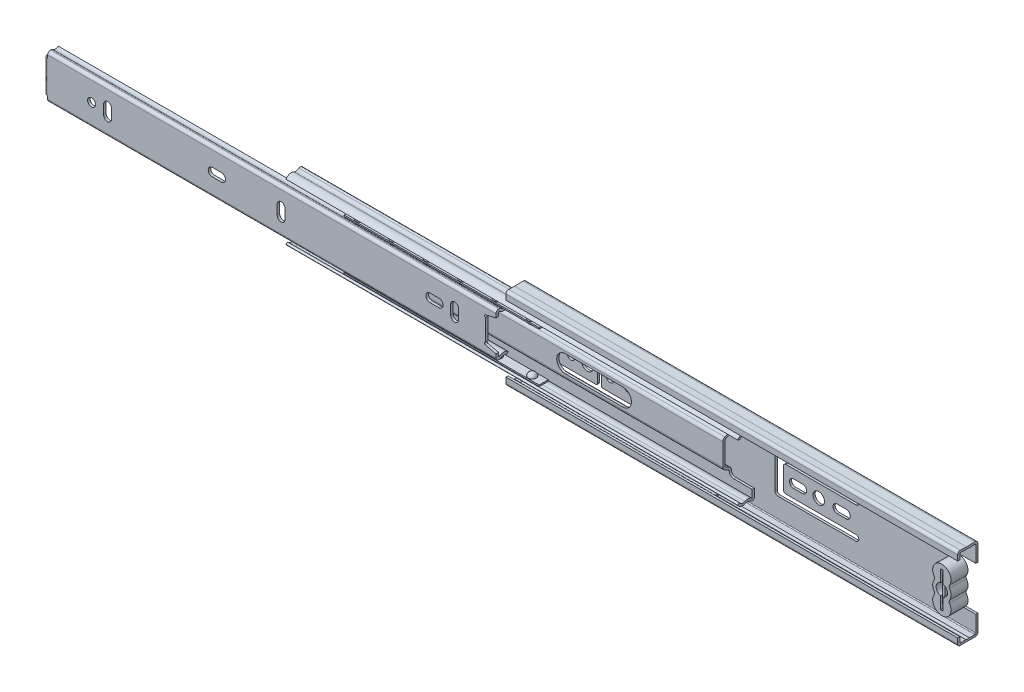
SolidWorks part; units mm, degrees
ref_plane "Front" through (0, 0, 0) normal (0, 0, 1) x (1, 0, 0)
ref_plane "Top" through (0, 0, 0) normal (0, 1, 0) x (1, 0, 0)
ref_plane "Right" through (0, 0, 0) normal (1, 0, 0) x (0, 0, -1)
sketch "Sketch1" plane through (0, 0, 0) normal (1, 0, 0) x (0, 0, -1)
  line L1 (5.6388, 0) -> (-5.6388, 0) construction
  line L4 (-4.1393, 22.8203) -> (-0.7433, 22.6989)
  line L5 (-1.1312, 21.5182) -> (-4.1819, 21.6273)
  line L6 (-4.445, 18.415) -> (-5.6388, 18.415)
  line L7 (-4.445, 21.3734) -> (-4.445, 18.415)
  line L8 (-5.6388, 18.415) -> (-5.6388, 21.3734)
  line L9 (3.9237, 21.6269) -> (0.7619, 21.5441)
  line L10 (5.6388, 0) -> (5.6388, 21.1191)
  line L11 (4.445, 21.1191) -> (4.445, 0)
  line L12 (5.6388, 0) -> (4.445, 0)
  line L13 (-0.7433, 22.6989) -> (3.8925, 22.8203)
  arc A0 (-4.445, 21.3734) -> (-4.1819, 21.6273) centre (-4.191, 21.3734) cw
  arc A1 (-5.6388, 21.3734) -> (-4.1393, 22.8203) centre (-4.191, 21.3734) cw
  arc A3 (3.9237, 21.6269) -> (4.445, 21.1191) centre (3.937, 21.1191) cw
  arc A4 (3.8925, 22.8203) -> (5.6388, 21.1191) centre (3.937, 21.1191) cw
  arc A5 (-1.1312, 21.5182) -> (0.7619, 21.5441) centre (-0.1524, 19.1744) cw
  dimension "D2" = 19.1744
  dimension "D7" = 0.254
  dimension "D8" = 0.508
  dimension "D6" = 2.54
  dimension "D9" = 1.1938
  dimension "D10" = 88.5
  dimension "D1" = 11.2776
  dimension "D3" = 5.7912
  dimension "D4" = 36.83
  dimension "D5" = 1.1938
  dimension "D11" = 87.953
  dimension "D12" = 45.6406
extrude "Extrude1" add sketch "Sketch1" along normal mid plane 249.936
ref_plane "Travel / 2" through (-246.6102, 0, 0) normal (-1, 0, 0) x (0, 0, 1)
sketch "Sketch2" plane through (-246.6102, 0, 0) normal (-1, 0, 0) x (0, 0, 1)
  line L0 (0.0254, 6.1159) -> (0.0254, 0)
  line L2 (-5.6388, 0) -> (5.6388, 0) construction
  line L3 (5.6388, 21.3734) -> (5.6388, 18.415) construction
  line L7 (-4.445, 21.1191) -> (-4.445, 0) construction
  line L8 (-5.6388, 0) -> (-5.6388, 21.1191) construction
  line L13 (-3.5306, 16.3766) -> (-3.5306, 9.5217)
  line L46 (-2.3867, 7.7262) -> (-0.4146, 6.8065)
  arc A0 (0.0254, 6.1159) -> (-0.4146, 6.8065) centre (-0.7366, 6.1159) ccw
  arc A1 (-1.5056, 17.2916) -> (1.2415, 16.9143) centre (0.1524, 19.1744) ccw
  arc A4 (1.1312, 21.5182) -> (-0.7619, 21.5441) centre (0.1524, 19.1744) ccw construction
  arc A19 (-3.5306, 9.5217) -> (-2.3867, 7.7262) centre (-1.5494, 9.5217) ccw
  arc A25 (-1.5056, 17.2916) -> (-3.5306, 16.3766) centre (-2.3114, 16.3766) ccw
  arc A51 (5.7404, 15.6277) -> (1.2415, 16.9143) centre (2.7686, 13.7451) ccw
  dimension "D2" = 8.4074
  dimension "D3" = 27.4903
  dimension "D6" = 1.9812
  dimension "D8" = 12.2319
  dimension "D10" = 2.5088
  dimension "D11" = 1.2192
  dimension "D4" = 0.762
  dimension "D5" = 4.4704
  dimension "D7" = 115
  dimension "D9" = 19.0435
  dimension "D13" = 11.3792
extrude "Middle Member" add sketch "Sketch2" against normal blind 249.936 separate body thin thin type one direction reverse wall 1.2192
ref_plane "Travel" through (-378.968, 0, 0) normal (-1, 0, 0) x (0, 0, 1)
sketch "Sketch3" plane through (-378.968, 0, 0) normal (-1, 0, 0) x (0, 0, 1)
  line L0 (1.2446, 0) -> (0.0254, 0) construction
  line L1 (-5.6388, 0) -> (-5.6388, 21.1191) construction
  line L56 (7.0612, 0) -> (7.0612, 10.6235)
  line L93 (5.5372, 12.1475) -> (5.1643, 12.1475)
  arc A0 (1.2082, 11.9072) -> (4.2365, 11.8325) centre (2.7686, 13.7451) ccw
  arc A29 (7.0612, 10.6235) -> (5.5372, 12.1475) centre (5.5372, 10.6235) ccw
  arc A53 (5.1643, 12.1475) -> (4.2365, 11.8325) centre (5.1643, 10.6235) ccw
  dimension "D1" = 1.524
  dimension "D4" = 1.524
  dimension "D5" = 2.411
  dimension "D2" = 12.7
  dimension "D3" = 12.1475
  dimension "D6" = 5.853
extrude "Drawer Member" add sketch "Sketch3" against normal blind 249.936 thin thin type one direction wall 1.397
sketch "Sketch6" plane through (0, 0, 7.0612) normal (0, 0, 1) x (1, 0, 0)
  line L1 (-378.968, 0) -> (-377.063, 0)
  line L2 (-378.968, 0) -> (-378.968, 12.1475)
  line L3 (-378.968, 12.1475) -> (-377.063, 12.1475)
  line L4 (-377.063, 0) -> (-377.063, 12.1475)
  line L5 (-129.032, 12.1475) -> (-378.968, 12.1475) construction
  line L7 (-378.968, 10.6235) -> (-378.968, 0) construction
  line L8 (-129.032, 0) -> (-378.968, 0) construction
  dimension "D1" = 1.905
extrude "Cut-Extrude1" cut sketch "Sketch6" against normal through all
sketch "Sketch7" plane through (0, 0, 0) normal (0, -1, 0) x (1, 0, 0)
  line L0 (-377.063, 7.0612) -> (-377.317, 7.0612)
  line L1 (-378.968, 5.4102) -> (-378.968, 0.3041)
  line L2 (-378.968, 0.3041) -> (-377.571, 0.3041)
  line L3 (-377.571, 0.3041) -> (-377.571, 5.4102)
  line L4 (-377.317, 5.6642) -> (-377.063, 5.6642)
  line L5 (-129.032, 5.6642) -> (-377.063, 5.6642) construction
  line L6 (-377.063, 7.0612) -> (-377.063, 5.6642)
  line L7 (-129.032, 0.3041) -> (-377.063, 0.3041) construction
  line L9 (-377.063, 5.087) -> (-377.063, 0.3041) construction
  arc A0 (-377.317, 5.6642) -> (-377.571, 5.4102) centre (-377.317, 5.4102) ccw
  arc A1 (-377.317, 7.0612) -> (-378.968, 5.4102) centre (-377.317, 5.4102) ccw
  dimension "D1" = 0.254
  dimension "D2" = 1.905
extrude "Extrude4" add sketch "Sketch7" against normal blind 8.89
sketch "Sketch8" plane through (0, 0, -4.445) normal (0, 0, 1) x (1, 0, 0)
  line L0 (115.3295, 7.6456) -> (116.7638, 7.493)
  line L1 (124.968, 12.2048) -> (115.5714, 12.2048)
  line L2 (116.7638, 7.493) -> (116.7638, 0)
  line L3 (124.968, 0) -> (-124.968, 0) construction
  line L4 (124.968, 21.1191) -> (124.968, 0) construction
  line L5 (124.968, 12.2048) -> (124.968, 0)
  line L6 (124.968, 0) -> (116.7638, 0)
  arc A0 (115.5714, 12.2048) -> (115.3295, 7.6456) centre (115.5714, 9.9188) ccw
  dimension "D3" = 9.9188
  dimension "D1" = 12.2048
  dimension "D2" = 8.2042
  dimension "D4" = 9.3966
  dimension "D5" = 7.493
extrude "Cut-Extrude2" cut sketch "Sketch8" against normal up to next (1.1938 mm away)
sketch "Sketch9" plane through (0, 0, -4.445) normal (0, 0, 1) x (1, 0, 0)
  line L0 (116.7638, 0) -> (-124.968, 0) construction
  line L1 (116.7638, 7.493) -> (115.3668, 7.493)
  line L2 (116.7638, 7.493) -> (116.7638, 0)
  line L3 (116.7638, 0) -> (115.3668, 0)
  line L4 (115.3668, 7.493) -> (115.3668, 0)
  dimension "D1" = 1.397
extrude "Extrude5" add sketch "Sketch9" along normal up to surface (8.89 mm away) up to face at (0, 19.8942, 4.445)
sketch "Sketch10" plane through (0, 0, 4.445) normal (0, 0, 1) x (1, 0, 0)
  line L0 (110.9853, 0) -> (112.8903, 0)
  line L1 (115.3509, 9.8425) -> (116.7797, 9.8425)
  line L2 (115.3509, 3.0936) -> (115.3509, 9.8425)
  line L3 (116.7797, 3.0936) -> (116.7797, 9.8425)
  line L6 (119.2403, 0) -> (121.1453, 0)
  line L7 (115.3668, 0) -> (-124.968, 0) construction
  line L8 (116.0653, 0) -> (116.0653, 4.4715) construction
  line L9 (115.3668, 0) -> (116.7638, 0) construction
  arc A0 (121.1453, 0) -> (120.3355, 2.7517) centre (116.0653, 0) ccw
  arc A1 (120.3355, 4.4715) -> (120.3355, 2.7517) centre (121.67, 3.6116) ccw
  arc A2 (120.3355, 4.4715) -> (111.7951, 4.4715) centre (116.0653, 7.2231) ccw
  arc A3 (111.7951, 2.7517) -> (111.7951, 4.4715) centre (110.4606, 3.6116) ccw
  arc A4 (111.7951, 2.7517) -> (110.9853, 0) centre (116.0653, 0) ccw
  arc A5 (115.3509, 3.0936) -> (112.8903, 0) centre (116.0653, 0) ccw
  arc A6 (119.2403, 0) -> (116.7797, 3.0936) centre (116.0653, 0) ccw
  dimension "D1" = 3.175
  dimension "D2" = 5.08
  dimension "D5" = 5.08
  dimension "D6" = 1.5875
  dimension "D3" = 9.8425
  dimension "D4" = 1.4288
  dimension "D7" = 7.2231
extrude "Extrude6" add sketch "Sketch10" along normal blind 1.016 and the other way offset from surface 0.508 separate body other way up to face at (64.0263, 9.9327, -4.445)
sketch "Sketch11" plane through (0, 0, 7.0612) normal (0, 0, 1) x (1, 0, 0)
  line L0 (-134.747, 5.9678) -> (-134.747, 0)
  line L8 (-129.032, 8.5893) -> (-134.8913, 7.2212)
  line L11 (-134.747, 0) -> (-129.032, 0)
  line L12 (-129.032, 0) -> (-129.032, 8.5893)
  arc A1 (-134.8913, 7.2212) -> (-134.747, 5.9678) centre (-134.7469, 6.6028) ccw
  dimension "D3" = 0.635
  dimension "D1" = 5.715
  dimension "D2" = 8.5893
  dimension "D4" = 5.9678
  dimension "D5" = 103.143
extrude "Cut-Extrude3" cut sketch "Sketch11" against normal up to next (1.397 mm away)
sketch "Sketch12" plane through (0, 0, 1.2446) normal (0, 0, 1) x (1, 0, 0)
  line L0 (3.3258, 12.065) -> (-6.8342, 12.065)
  line L1 (3.3258, 16.3766) -> (3.3258, 9.5217) construction
  line L2 (-9.3742, 9.525) -> (-9.3742, 0)
  line L3 (3.3258, 0) -> (-246.6102, 0) construction
  line L4 (-9.3742, 0) -> (3.3258, 0)
  line L5 (3.3258, 0) -> (3.3258, 12.065)
  arc A0 (-6.8342, 12.065) -> (-9.3742, 9.525) centre (-6.8342, 9.525) ccw
  point P11 (-9.3742, 12.065)
  dimension "D3" = 2.54
  dimension "D1" = 12.7
  dimension "D2" = 12.065
extrude "Cut-Extrude4" cut sketch "Sketch12" against normal through all
sketch "Sketch13" plane through (0, 0, -4.445) normal (0, 0, 1) x (1, 0, 0)
  line L0 (-56.5797, 7.112) -> (-81.4082, 7.112)
  line L1 (115.3668, 0) -> (-124.968, 0) construction
  line L2 (-64.6696, 0) -> (-64.6696, 4.2392) construction
  line L3 (-107.5067, 10.287) -> (-56.5797, 10.287)
  line L4 (-124.968, 21.1191) -> (-124.968, 0) construction
  line L5 (-85.2182, 7.112) -> (-107.5067, 7.112)
  line L6 (-84.4562, 0) -> (-84.4562, 6.35)
  line L7 (-82.1702, 6.35) -> (-82.1702, 0)
  line L8 (-62.1931, 2.286) -> (-67.1461, 2.286)
  line L13 (-101.2456, 0) -> (-96.6736, 0)
  line L14 (-93.143, 0) -> (-86.793, 0)
  line L15 (-84.4562, 0) -> (-82.1702, 0)
  line L16 (-79.6556, 0) -> (-75.0836, 0)
  line L17 (-69.4321, 0) -> (-59.9071, 0)
  arc A1 (-107.5067, 10.287) -> (-107.5067, 7.112) centre (-107.5067, 8.6995) ccw
  arc A2 (-84.4562, 6.35) -> (-85.2182, 7.112) centre (-85.2182, 6.35) ccw
  arc A4 (-81.4082, 7.112) -> (-82.1702, 6.35) centre (-81.4082, 6.35) ccw
  arc A7 (-56.5797, 7.112) -> (-56.5797, 10.287) centre (-56.5797, 8.6995) ccw
  arc A8 (-86.793, 0) -> (-93.143, 0) centre (-89.968, 0) ccw
  arc A9 (-96.6736, 0) -> (-101.2456, 0) centre (-98.9596, 0) ccw
  arc A10 (-75.0836, 0) -> (-79.6556, 0) centre (-77.3696, 0) ccw
  arc A11 (-59.9071, 0) -> (-62.1931, 2.286) centre (-62.1931, 0) ccw
  arc A12 (-67.1461, 2.286) -> (-69.4321, 0) centre (-67.1461, 0) ccw
  dimension "D3" = 2.286
  dimension "D4" = 3.175
  dimension "D7" = 8.9916
  dimension "D8" = 21.59
  dimension "D9" = 34.29
  dimension "D10" = 0.762
  dimension "D11" = 17.5387
  dimension "D12" = 9.525
  dimension "D13" = 5.5118
  dimension "D14" = 35
  dimension "D1" = 3.175
  dimension "D2" = 50.927
  dimension "D5" = 2.286
  dimension "D6" = 10.287
extrude "Cut-Extrude5" cut sketch "Sketch13" against normal up to next (1.1938 mm away)
sketch "Sketch32" plane through (0, 0, -5.6388) normal (0, 0, -1) x (-1, 0, 0)
  line L0 (-55.4945, 0) -> (-45.9695, 0)
  line L1 (-41.207, 0) -> (-34.857, 0)
  line L2 (-31.3645, 0) -> (-21.8395, 0)
  line L3 (-18.474, 0) -> (-13.902, 0)
  line L4 (-116.7638, 0) -> (59.9071, 0) construction
  line L5 (107.5067, 10.287) -> (56.5797, 10.287) construction
  line L6 (56.5797, 7.112) -> (81.4082, 7.112) construction
  line L7 (-26.602, 2.286) -> (-26.602, -3.4269) construction
  line L8 (-50.732, 2.286) -> (-50.732, -3.4269) construction
  line L14 (-58.6695, 10.287) -> (-15.426, 10.287)
  line L15 (-19.998, 7.112) -> (-58.6695, 7.112)
  line L17 (-13.902, 8.763) -> (-13.902, 0)
  line L18 (-18.474, 0) -> (-18.474, 5.588)
  line L23 (-53.2085, 2.286) -> (-48.2555, 2.286)
  line L25 (-29.0785, 2.286) -> (-24.1255, 2.286)
  arc A0 (93.143, 0) -> (86.793, 0) centre (89.968, 0) ccw construction
  arc A13 (-13.902, 8.763) -> (-15.426, 10.287) centre (-15.426, 8.763) ccw
  arc A14 (-18.474, 5.588) -> (-19.998, 7.112) centre (-19.998, 5.588) ccw
  arc A17 (-58.6695, 10.287) -> (-58.6695, 7.112) centre (-58.6695, 8.6995) ccw
  arc A20 (-45.9695, 0) -> (-48.2555, 2.286) centre (-48.2555, 0) ccw
  arc A21 (-53.2085, 2.286) -> (-55.4945, 0) centre (-53.2085, 0) ccw
  arc A22 (-34.857, 0) -> (-41.207, 0) centre (-38.032, 0) ccw
  arc A24 (-21.8395, 0) -> (-24.1255, 2.286) centre (-24.1255, 0) ccw
  arc A25 (-29.0785, 2.286) -> (-31.3645, 0) centre (-29.0785, 0) ccw
  dimension "D2" = 1.524
  dimension "D3" = 3.175
  dimension "D4" = 9.525
  dimension "D5" = 2.286
  dimension "D6" = 11.43
  dimension "D7" = 12.7
  dimension "D8" = 24.13
  dimension "D9" = 20.6375
  dimension "D10" = 128
  dimension "D1" = 4.572
extrude "Cut-Extrude14" cut sketch "Sketch32" against normal up to next (1.1938 mm away)
sketch "Sketch31" plane through (0, 0, -5.6388) normal (0, 0, -1) x (-1, 0, 0)
  line L0 (-124.968, 12.2048) -> (-124.968, 21.1191) construction
  line L1 (-116.7638, 0) -> (-55.4945, 0) construction
  line L2 (-109.093, 0) -> (-102.743, 0)
  arc A0 (-102.743, 0) -> (-109.093, 0) centre (-105.918, 0) ccw
  dimension "D1" = 19.05
  dimension "D2" = 6.35
extrude "Cut-Extrude15" cut sketch "Sketch31" against normal up to next (1.1938 mm away)
sketch "Sketch24" plane through (0, 0, 7.0612) normal (0, 0, 1) x (1, 0, 0)
  line L0 (-134.747, 0) -> (-377.317, 0) construction
  line L1 (-343.916, 4.826) -> (-343.916, 0) construction
  line L2 (-346.1004, 2.6416) -> (-346.1004, 0)
  line L3 (-346.1004, 0) -> (-341.7316, 0)
  line L4 (-341.7316, 0) -> (-341.7316, 2.6416)
  line L5 (-288.2265, 0) -> (-278.7015, 0)
  line L6 (-285.9405, 2.286) -> (-280.9875, 2.286)
  line L8 (-250.0884, 2.6416) -> (-250.0884, 0)
  line L9 (-250.0884, 0) -> (-245.7196, 0)
  line L10 (-245.7196, 0) -> (-245.7196, 2.6416)
  line L11 (-378.968, 8.89) -> (-378.968, 0) construction
  line L12 (-283.464, 2.286) -> (-283.464, 0) construction
  circle A0 centre (-352.806, 0) radius 2.1844
  arc A1 (-346.1004, 2.6416) -> (-341.7316, 2.6416) centre (-343.916, 2.6416) cw
  arc A2 (-288.2265, 0) -> (-285.9405, 2.286) centre (-285.9405, 0) cw
  arc A3 (-280.9875, 2.286) -> (-278.7015, 0) centre (-280.9875, 0) cw
  arc A4 (-250.0884, 2.6416) -> (-245.7196, 2.6416) centre (-247.904, 2.6416) cw
  dimension "D1" = 4.3688
  dimension "D4" = 8.89
  dimension "D5" = 2.286
  dimension "D7" = 60.452
  dimension "D8" = 96.012
  dimension "D2" = 35.052
  dimension "D3" = 4.826
  dimension "D6" = 9.525
extrude "Cut-Extrude13" cut sketch "Sketch24" against normal up to next (1.397 mm away)
sketch "Sketch25" plane through (0, 0, 7.0612) normal (0, 0, 1) x (1, 0, 0)
  line L0 (-154.0764, 0) -> (-149.7076, 0)
  line L1 (-134.747, 0) -> (-245.7196, 0) construction
  line L2 (-149.7076, 0) -> (-149.7076, 2.6416)
  line L3 (-154.0764, 2.6416) -> (-154.0764, 0)
  line L4 (-245.7196, 0) -> (-245.7196, 2.6416) construction
  line L5 (-158.3055, 0) -> (-167.8305, 0)
  line L6 (-280.9875, 2.286) -> (-285.9405, 2.286) construction
  line L7 (-165.5445, 2.286) -> (-160.5915, 2.286)
  line L8 (-163.068, 0) -> (-163.068, 2.286) construction
  arc A0 (-149.7076, 2.6416) -> (-154.0764, 2.6416) centre (-151.892, 2.6416) ccw
  arc A1 (-245.7196, 2.6416) -> (-250.0884, 2.6416) centre (-247.904, 2.6416) ccw construction
  arc A2 (-341.7316, 2.6416) -> (-346.1004, 2.6416) centre (-343.916, 2.6416) ccw construction
  arc A3 (-165.5445, 2.286) -> (-167.8305, 0) centre (-165.5445, 0) ccw
  arc A4 (-160.5915, 2.286) -> (-158.3055, 0) centre (-160.5915, 0) cw
  arc A5 (-278.7015, 0) -> (-280.9875, 2.286) centre (-280.9875, 0) ccw construction
  dimension "D1" = 192.024
  dimension "D2" = 11.176
extrude "Cut E" cut sketch "Sketch25" against normal up to next (1.397 mm away)
sketch "Sketch26" plane through (0, 0, 1.2446) normal (0, 0, 1) x (1, 0, 0)
  line L0 (-101.2456, 0) -> (-59.9071, 0)
  line L1 (-96.4196, 4.826) -> (-64.7331, 4.826)
  line L2 (55.4945, 0) -> (21.8395, 0)
  line L3 (26.6655, 4.826) -> (50.6685, 4.826)
  arc A0 (-101.2456, 0) -> (-96.4196, 4.826) centre (-96.4196, 0) cw
  arc A1 (-59.9071, 0) -> (-64.7331, 4.826) centre (-64.7331, 0) ccw
  arc A2 (21.8395, 0) -> (26.6655, 4.826) centre (26.6655, 0) cw
  arc A3 (50.6685, 4.826) -> (55.4945, 0) centre (50.6685, 0) cw
  arc A5 (24.1255, 2.286) -> (21.8395, 0) centre (24.1255, 0) ccw construction
  dimension "D1" = 4.826
extrude "Cut-Extrude17" cut sketch "Sketch26" against normal up to next (1.2192 mm away)
ref_plane "Plane3" through (-112.268, 0, 0) normal (-1, 0, 0) x (0, 0, 1)
sketch "Sketch27" plane through (-112.268, 0, 0) normal (-1, 0, 0) x (0, 0, 1)
  line L0 (0.1524, 21.6832) -> (0.1524, 16.6656)
  line L1 (0.1524, 23.635) -> (0.1524, 15.2838) construction
  arc A0 (0.1524, 16.6656) -> (0.1524, 21.6832) centre (0.1524, 19.1744) ccw
  arc A1 (-1.5056, 17.2916) -> (1.2415, 16.9143) centre (0.1524, 19.1744) ccw construction
revolve "Revolve1" add sketch "Sketch27" angle 360 about L1
pattern_linear "LPattern1" count 6 spacing 19.05 along (1, 0, 0) of bodies 128
sketch "Sketch28" plane through (-112.268, 0, 0) normal (-1, 0, 0) x (0, 0, 1)
  line L0 (2.6612, 19.1744) -> (-2.3564, 19.1744) construction
  line L1 (3.9624, 18.7934) -> (-3.6576, 18.7934)
  line L2 (3.9624, 18.7934) -> (3.9624, 19.5554)
  line L3 (3.9624, 19.5554) -> (-3.6576, 19.5554)
  line L4 (-3.6576, 18.7934) -> (-3.6576, 19.5554)
  line L5 (0.1524, 20.5465) -> (0.1524, 17.804) construction
  circle A1 centre (0.1524, 19.1744) radius 2.5088 construction
  point P8 (0.1524, 19.1744)
  dimension "D1" = 7.62
  dimension "D2" = 0.762
extrude "Extrude7" add sketch "Sketch28" along normal blind 6.35 and the other way blind 101.6
ref_plane "Plane4" through (-208.5102, 0, 0) normal (-1, 0, 0) x (0, 0, 1)
sketch "Sketch29" plane through (-208.5102, 0, 0) normal (-1, 0, 0) x (0, 0, 1)
  line L0 (2.7686, 16.0438) -> (2.7686, 11.4464)
  line L1 (2.7686, 16.6801) -> (2.7686, 10.2973) construction
  arc A0 (2.7686, 11.4464) -> (2.7686, 16.0438) centre (2.7686, 13.7451) ccw
  arc A1 (4.7105, 14.9753) -> (1.7707, 15.816) centre (2.7686, 13.7451) ccw construction
revolve "Revolve2" add sketch "Sketch29" angle 360 about L1
pattern_linear "LPattern2" count 6 spacing 19.05 along (1, 0, 0) of bodies 135
sketch "Sketch30" plane through (-208.5102, 0, 0) normal (-1, 0, 0) x (0, 0, 1)
  line L0 (0.4699, 13.7451) -> (5.0673, 13.7451) construction
  line L1 (3.9624, 18.7934) -> (3.9624, 19.5554) construction
  line L2 (0.2286, 14.1261) -> (5.3086, 14.1261)
  line L3 (0.2286, 14.1261) -> (0.2286, 13.3641)
  line L4 (0.2286, 13.3641) -> (5.3086, 13.3641)
  line L5 (5.3086, 14.1261) -> (5.3086, 13.3641)
  line L7 (2.7686, 14.2437) -> (2.7686, 12.7853) construction
  circle A0 centre (2.7686, 13.7451) radius 2.2987 construction
  point P4 (2.7686, 13.7451)
  dimension "D1" = 5.08
extrude "Extrude8" add sketch "Sketch30" along normal blind 6.35 and the other way blind 101.6
mirror "Mirror3" about plane through (0, 0, 0) normal (0, 1, 0) of bodies 117 126 163 159 124 127 119
mirror "Mirror5" about plane through (0, 0, 0) normal (0, 1, 0) of bodies 141 134
